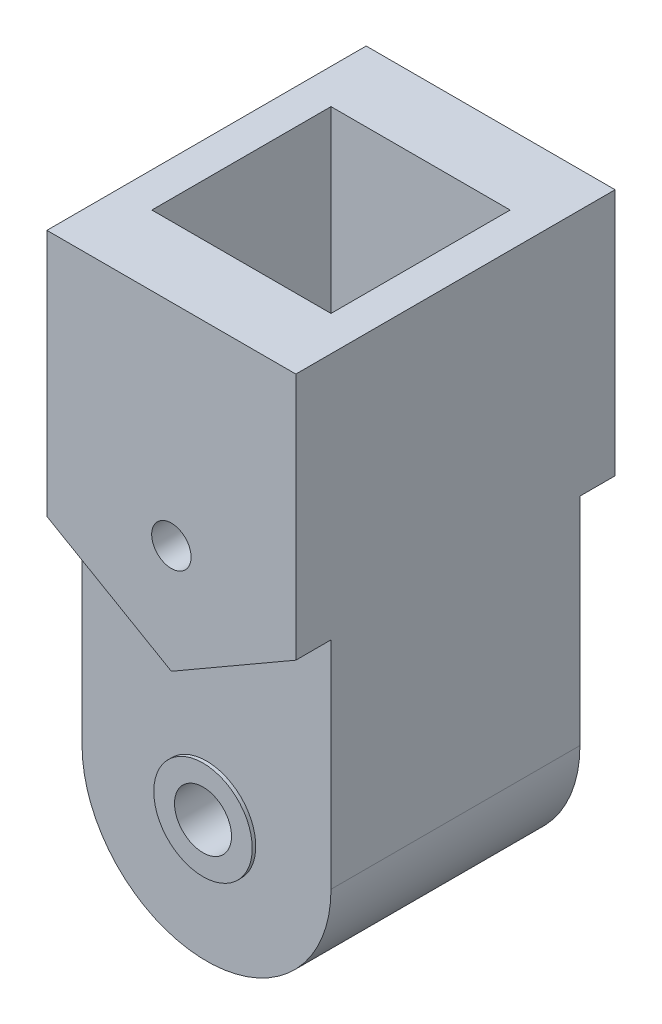
SolidWorks part; units mm, degrees
material "PETG"
ref_plane "Front Plane" through (0, 0, 0) normal (0, 0, 1) x (1, 0, 0)
ref_plane "Top Plane" through (0, 0, 0) normal (0, 1, 0) x (1, 0, 0)
ref_plane "Right Plane" through (0, 0, 0) normal (1, 0, 0) x (0, 0, -1)
sketch "Sketch1" plane through (0, 0, 0) normal (0, 1, 0) x (1, 0, 0)
  line L1 (-12.7375, -12.7375) -> (12.7375, -12.7375)
  line L2 (-12.7375, -12.7375) -> (-12.7375, 12.7375)
  line L3 (-12.7375, 12.7375) -> (12.7375, 12.7375)
  line L4 (12.7375, -12.7375) -> (12.7375, 12.7375)
  line L5 (-17.7, -17.7) -> (17.7, -17.7)
  line L6 (-17.7, -17.7) -> (-17.7, 17.7)
  line L7 (-17.7, 17.7) -> (17.7, 17.7)
  line L8 (17.7, -17.7) -> (17.7, 17.7)
  point P8 (0, -17.7)
  point P9 (0, -12.7375)
  point P12 (-17.7, 0)
  point P13 (-12.7375, 0)
  dimension "D1" = 25.475
  dimension "D2" = 35.4
extrude "Boss-Extrude1" add sketch "Sketch1" along normal blind 50.0375
extrude "Boss-Extrude2" add sketch "Sketch1<3>" against normal blind 9.9625 contours L1 L4 L3 L2 | L5 L8 L7 L6 L4 L1 L2 L3 region at (0, 0, 0) region at (-17.1994, 0, 0)
sketch "Sketch1<3>" plane through (0, 0, 0) normal (0, 1, 0) x (1, 0, 0) same geometry as "Sketch1"
sketch "Sketch2" plane through (0, 0, -17.7) normal (0, 0, 1) x (1, 0, 0)
  line L1 (17.7, 50.0375) -> (17.7, -9.9625) construction
  line L4 (-17.7, -9.9625) -> (17.7, -9.9625) construction
  line L5 (-17.7, -15.9125) -> (-17.7, -9.9625)
  line L6 (17.7, -9.9625) -> (17.7, -15.9125)
  line L7 (17.7, -9.9625) -> (-17.7, -9.9625)
  circle A0 centre (0, -15.9625) radius 4.05
  circle A2 centre (0, -15.9625) radius 11 construction
  arc A3 (17.7, -15.9125) -> (-17.7, -15.9125) centre (0, -15.9125) cw
  dimension "D1" = 8.1
  dimension "D3" = 22
  dimension "D2" = 6
  dimension "D4" = 5.95
extrude "Boss-Extrude5" add sketch "Sketch2" along normal up to surface (35.4 mm away) up to face at (0, 20.0375, 17.7)
ref_plane "Plane1" through (0, -33.6125, 0) normal (0, -1, 0) x (-1, 0, 0)
sketch "Sketch3" plane through (0, -33.6125, 0) normal (0, -1, 0) x (-1, 0, 0)
  circle A0 centre (0, 0) radius 3.15
  dimension "D1" = 6.3
extrude "Cut-Extrude1" cut sketch "Sketch3" against normal through all
sketch "Sketch4" plane through (0, -33.6125, 0) normal (0, -1, 0) x (-1, 0, 0)
  circle A0 centre (0, 0) radius 5.5
  dimension "D1" = 11
extrude "Cut-Extrude2" cut sketch "Sketch4" against normal offset from surface (25.6125 mm away) 8 up to face at (0, 0, 3.15)
sketch "Sketch5" plane through (0, 0, 17.7) normal (0, 0, 1) x (1, 0, 0)
  circle A0 centre (0, -15.9625) radius 7
  circle A1 centre (0, -15.9625) radius 4.05 construction
  circle M6 centre (0, -15.9625) radius 4.05
  dimension "D1" = 14
extrude "Boss-Extrude6" add sketch "Sketch5" along normal blind 0.5 contours A0 M6 region at (-6.802, -15.9625, 17.7)
mirror "Mirror1" about plane through (0, 0, 0) normal (0, 0, 1) of "Boss-Extrude6"
sketch "Sketch6" plane through (0, 0, 17.7) normal (0, 0, 1) x (1, 0, 0)
  line L5 (8.875, -31.2845) -> (52.1763, -6.2845) construction
  line L6 (-8.875, -0.5405) -> (34.4263, 24.4595) construction
  line L7 (52.1763, -6.2845) -> (34.4263, 24.4595) construction
  line L8 (0, -16) -> (0, -79.4793) construction
  line L9 (17.7, 50.0375) -> (17.7, -15.9125) construction
  line L10 (17.7, 14.8025) -> (-17.7, 14.8025)
  line L11 (17.7, 14.8025) -> (17.7, 50.0375)
  line L12 (17.7, 50.0375) -> (-17.7, 50.0375)
  line L13 (-17.7, 14.8025) -> (-17.7, 50.0375)
  line L14 (17.7, 14.8025) -> (0, 4.5834)
  line L15 (0, 4.5834) -> (-17.7, 14.8025)
  circle A1 centre (0, -15.9125) radius 17.75
  arc A2 (-17.7, -15.9125) -> (17.7, -15.9125) centre (0, -15.9125) ccw construction
  line M4 (-17.7, 50.0375) -> (-17.7, -15.9125)
  line M6 (17.7, -15.9125) -> (17.7, 50.0375)
  line M7 (17.7, 50.0375) -> (-17.7, 50.0375)
  dimension "D1" = 50
  dimension "D2" = 120
  dimension "D3" = 35.5
extrude "Boss-Extrude7" add sketch "Sketch6" along normal blind 5 contours L14 L10 M4 | L10 M6 M7 M4 region at (0, 11.3962, 17.7) region at (0, 32.42, 17.7)
sketch "Sketch7" plane through (0, 0, 22.7) normal (0, 0, 1) x (1, 0, 0)
  line L0 (17.7, 50.0375) -> (-17.7, 50.0375) construction
  line L1 (17.7, 20.0375) -> (0, 20.0375) construction
  line L2 (17.7, 14.8025) -> (17.7, 50.0375) construction
  line L3 (0, 20.0375) -> (-17.7, 20.0375) construction
  line L4 (-17.7, 50.0375) -> (-17.7, 14.8025) construction
  circle A0 centre (0, 20.0375) radius 2.8
  dimension "D1" = 30
  dimension "D2" = 5.6
extrude "Cut-Extrude3" cut sketch "Sketch7" against normal up to next
mirror "Mirror2" about plane through (0, 0, 0) normal (0, 0, 1) of "Boss-Extrude7", "Cut-Extrude3"
equation "\"tol_dia_id_intfc\" = 0.0500mm ' For hole diameters - Interference fit"
equation "\"tol_dia_id_slip\"  = 0.0750mm ' For hole diameters - Slip fit"
equation "\"tol_dia_id_clear\" = 0.1000mm ' For hole diameters - Clearance fit"
equation "\"tol_dia_od_intfc\" = 0.0500mm ' For shaft diameters - Interference fit"
equation "\"tol_dia_od_slip\"  = 0.0750mm ' For shaft diameters - Slip fit"
equation "\"tol_dia_od_clear\" = 0.1000mm ' For shaft diameters - Clearance fit"
equation "\"tol_general_intfc\"= 0.0250mm ' For general parts (Horiz) - Interference fit"
equation "\"tol_general_slip\" = 0.0375mm ' For general parts (Horiz) - Slip fit"
equation "\"tol_general_clear\"= 0.0500mm ' For general parts (Horiz) - Clearance fit"
equation "\"tol_layer_intfc\"  = 0.0250mm ' For all parts (Vert) - Interference fit"
equation "\"tol_layer_slip\"   = 0.0375mm ' For all parts (Vert) - Slip fit"
equation "\"tol_layer_clear\"  = 0.0500mm ' For all parts (Vert) - Clearance fit"
equation "\"tol_corner_rad\"   = 0.100mm ' For corners that fit into other parts"
equation "\"D1@Sketch1\"=25.40mm+\"tol_general_slip\"*2"
equation "\"D2@Sketch1\"=25.4+10"
equation "\"D1@Boss-Extrude1\"= 50.00mm + \"tol_layer_slip\""
equation "\"D1@Boss-Extrude2\"=10.00mm-\"tol_layer_slip\""
equation "\"D1@Sketch2\"=8.00mm+\"tol_dia_id_clear\""
equation "\"D4@Sketch2\"=6.00mm-\"tol_dia_od_clear\"/2"
equation "\"D3@Sketch6\"=25.4+10+\"tol_general_clear\"*2"
